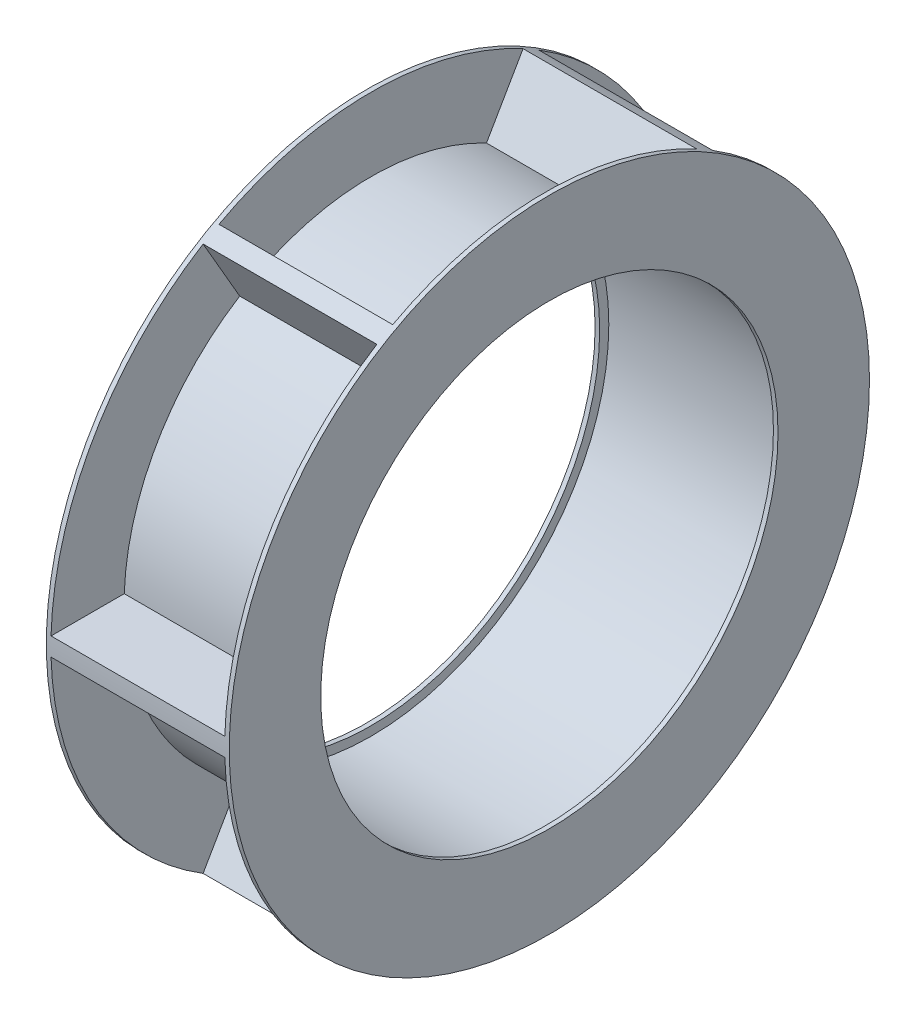
SolidWorks part; units mm, degrees
material "1060 Alloy"
ref_plane "Front Plane" through (0, 0, 0) normal (1, 0, 0) x (0, 1, 0)
ref_plane "Top Plane" through (0, 0, 0) normal (0, 0, 1) x (0, 1, 0)
ref_plane "Right Plane" through (0, 0, 0) normal (0, 1, 0) x (-1, 0, 0)
sketch "Sketch8" plane through (0, 0, 0) normal (1, 0, 0) x (0, 1, 0)
  circle A0 centre (0, 0) radius 125
  circle A1 centre (0, 0) radius 175
  dimension "D1" = 250
  dimension "D2" = 50
extrude "Boss-Extrude7" add sketch "Sketch8" along normal mid plane 100
sketch "Sketch9" plane through (0, 0, 0) normal (1, 0, 0) x (0, 1, 0)
  circle A0 centre (0, 0) radius 125 construction
  circle A1 centre (0, 0) radius 125
  circle A2 centre (0, 0) radius 130
  dimension "D1" = 5
extrude "Cut-Extrude2" cut sketch "Sketch9" against normal mid plane 95
sketch "Sketch10" plane through (50, 0, 0) normal (1, 0, 0) x (0, 1, 0)
  line L0 (0, -1000) -> (0, 49000) construction
  line L1 (149.0544, 91.8301) -> (110, 69.282)
  line L2 (-5, 175) -> (5, 175)
  line L3 (-5, 175) -> (-5, 129.9038)
  line L4 (-5, 129.9038) -> (5, 129.9038)
  line L5 (5, 175) -> (5, 129.9038)
  line L6 (149.0544, 91.8301) -> (154.0544, 83.1699)
  line L7 (154.0544, 83.1699) -> (115, 60.6218)
  line L8 (110, 69.282) -> (115, 60.6218)
  line L9 (154.0544, -83.1699) -> (115, -60.6218)
  line L10 (154.0544, -83.1699) -> (149.0544, -91.8301)
  line L11 (149.0544, -91.8301) -> (110, -69.282)
  line L12 (115, -60.6218) -> (110, -69.282)
  line L13 (5, -175) -> (5, -129.9038)
  line L14 (5, -175) -> (-5, -175)
  line L15 (-5, -175) -> (-5, -129.9038)
  line L16 (5, -129.9038) -> (-5, -129.9038)
  line L17 (-149.0544, -91.8301) -> (-110, -69.282)
  line L18 (-149.0544, -91.8301) -> (-154.0544, -83.1699)
  line L19 (-154.0544, -83.1699) -> (-115, -60.6218)
  line L20 (-110, -69.282) -> (-115, -60.6218)
  line L21 (-154.0544, 83.1699) -> (-115, 60.6218)
  line L22 (-154.0544, 83.1699) -> (-149.0544, 91.8301)
  line L23 (-149.0544, 91.8301) -> (-110, 69.282)
  line L24 (-115, 60.6218) -> (-110, 69.282)
  circle A0 centre (0, 0) radius 175 construction
  circle A1 centre (0, 0) radius 175
  circle A3 centre (0, 0) radius 130 construction
  circle A4 centre (0, 0) radius 135
  point P12 (0, 0)
  point P13 (0, 0)
  point P35 (0, 0)
  circle M12 centre (0, 0) radius 175
  dimension "D4" = 260
  dimension "D5" = 260
  dimension "D1" = 10
  dimension "D2" = 6
  dimension "D3" = 5
extrude "Cut-Extrude3" cut sketch "Sketch10" against normal through all both and the other way through all contours A3 L1 L5 M12 | A3 L9 L7 M12 | A3 L13 L11 M12 | A3 L17 L15 M12 | A3 L21 L19 M12 | A3 L3 L23 M12 region at (50, 74.8569, 129.656) region at (50, 149.7138, 0) region at (50, -74.8569, 129.656) region at (50, 74.8569, -129.656) region at (50, -149.7138, 0) region at (50, -74.8569, -129.656)
sketch "Sketch11" plane through (50, 0, 0) normal (1, 0, 0) x (0, 1, 0)
  circle A0 centre (0, 0) radius 125 construction
  circle A1 centre (0, 0) radius 125
  circle A2 centre (0, 0) radius 175
  dimension "D1" = 250
extrude "Boss-Extrude8" add sketch "Sketch11" against normal blind 2.5
mirror "Mirror3" about plane through (0, 0, 0) normal (1, 0, 0) of "Boss-Extrude8"
sketch "Sketch2" plane through (0, 0, 0) normal (1, 0, 0) x (0, 1, 0)
  line L0 (0, -1000) -> (0, 125) construction
  line L8 (-7.5, 23.8485) -> (-7.5, 125)
  line L9 (-7.5, 125) -> (7.5, 125)
  line L10 (7.5, 23.8485) -> (7.5, 125)
  line L11 (20.3636, 14.5025) -> (116.5644, 45.76)
  line L13 (24.9989, 0.2367) -> (121.1997, 31.4942)
  line L14 (116.5644, 45.76) -> (121.1997, 31.4942)
  line L15 (20.0854, -14.8854) -> (79.5408, -96.7187)
  line L17 (7.9502, -23.7022) -> (67.4055, -105.5355)
  line L18 (79.5408, -96.7187) -> (67.4055, -105.5355)
  line L19 (-7.9502, -23.7022) -> (-67.4055, -105.5355)
  line L21 (-20.0854, -14.8854) -> (-79.5408, -96.7187)
  line L22 (-67.4055, -105.5355) -> (-79.5408, -96.7187)
  line L23 (-24.9989, 0.2367) -> (-121.1997, 31.4942)
  line L25 (-20.3636, 14.5025) -> (-116.5644, 45.76)
  line L26 (-121.1997, 31.4942) -> (-116.5644, 45.76)
  line L31 (-962.4087, -312.7056) -> (118.8821, 38.6271) construction
  circle A0 centre (0, 0) radius 10
  circle A7 centre (0, 0) radius 25
  point P17 (0, 125)
  point P40 (0, 0)
  dimension "D1" = 20
  dimension "D2" = 50
  dimension "D3" = 125
  dimension "D4" = 15
  dimension "D6" = 125
  dimension "D5" = 5
extrude "Boss-Extrude1" [suppressed] add sketch "Sketch2" along normal mid plane 100
sketch "Sketch4" [suppressed] plane through (50, 0, 0) normal (1, 0, 0) x (0, 1, 0)
  line L0 (0, -1000) -> (0, 49000) construction
  line L1 (-1000, 0) -> (49000, 0) construction
  line L3 (-7.5, 125) -> (7.5, 125) construction
  circle A4 centre (0, 0) radius 125
  circle A5 centre (0, 0) radius 165
  dimension "D1" = 330
extrude "Boss-Extrude3" [suppressed] add sketch "Sketch4" against normal up to surface (100 mm away)
sketch "Sketch5" [suppressed] plane through (50, 0, 0) normal (1, 0, 0) x (0, 1, 0)
  line L0 (0, -1000) -> (0, 49000) construction
  line L34 (114.8915, 118.427) -> (90.1257, 93.6613)
  line L35 (-2.5, 165) -> (2.5, 165)
  line L36 (-2.5, 165) -> (-2.5, 129.976)
  line L37 (-2.5, 129.976) -> (2.5, 129.976)
  line L38 (2.5, 165) -> (2.5, 129.976)
  line L39 (114.8915, 118.427) -> (118.427, 114.8915)
  line L40 (118.427, 114.8915) -> (93.6613, 90.1257)
  line L41 (90.1257, 93.6613) -> (93.6613, 90.1257)
  line L42 (164.9677, 2.4866) -> (129.9436, 2.4866)
  line L43 (164.9677, 2.4866) -> (164.9677, -2.5134)
  line L44 (164.9677, -2.5134) -> (129.9436, -2.5134)
  line L45 (129.9436, 2.4866) -> (129.9436, -2.5134)
  line L46 (118.3947, -114.9049) -> (93.6289, -90.1391)
  line L47 (118.3947, -114.9049) -> (114.8591, -118.4404)
  line L48 (114.8591, -118.4404) -> (90.0934, -93.6746)
  line L49 (93.6289, -90.1391) -> (90.0934, -93.6746)
  line L50 (2.4543, -164.9811) -> (2.4543, -129.957)
  line L51 (2.4543, -164.9811) -> (-2.5457, -164.9811)
  line L52 (-2.5457, -164.9811) -> (-2.5457, -129.957)
  line L53 (2.4543, -129.957) -> (-2.5457, -129.957)
  line L54 (-114.9372, -118.4081) -> (-90.1714, -93.6423)
  line L55 (-114.9372, -118.4081) -> (-118.4727, -114.8725)
  line L56 (-118.4727, -114.8725) -> (-93.707, -90.1068)
  line L57 (-90.1714, -93.6423) -> (-93.707, -90.1068)
  line L58 (-165.0134, -2.4677) -> (-129.9894, -2.4677)
  line L59 (-165.0134, -2.4677) -> (-165.0134, 2.5323)
  line L60 (-165.0134, 2.5323) -> (-129.9894, 2.5323)
  line L61 (-129.9894, -2.4677) -> (-129.9894, 2.5323)
  line L62 (-118.4404, 114.9238) -> (-93.6746, 90.1581)
  line L63 (-118.4404, 114.9238) -> (-114.9049, 118.4593)
  line L64 (-114.9049, 118.4593) -> (-90.1391, 93.6936)
  line L65 (-93.6746, 90.1581) -> (-90.1391, 93.6936)
  circle A1 centre (0, 0) radius 130
  arc A3 (116.3503, 45.6905) -> (7.5, 124.7748) centre (0, 0) ccw construction
  circle A4 centre (0, 0) radius 165 construction
  circle A5 centre (0, 0) radius 165
  point P44 (-0.0229, 0.0095)
  dimension "D1" = 5
  dimension "D2" = 5
  dimension "D3" = 8
extrude "Cut-Extrude1" [suppressed] cut sketch "Sketch5" against normal blind 120
sketch "Sketch7" [suppressed] plane through (50, 0, 0) normal (1, 0, 0) x (0, 1, 0)
  circle A3 centre (0, 0) radius 130
  arc A4 (129.9762, 2.4866) -> (93.6746, 90.1391) centre (0, 0) ccw construction
  circle A5 centre (0, 0) radius 165
extrude "Boss-Extrude6" [suppressed] add sketch "Sketch7" against normal blind 4
mirror "Mirror2" [suppressed] about plane through (0, 0, 0) normal (1, 0, 0)
sketch "Sketch6" [suppressed] plane through (60, 0, 0) normal (1, 0, 0) x (0, 1, 0)
  line L0 (-14.4338, 25) -> (-28.8675, 0) construction
  line L1 (-28.8675, 0) -> (-14.4338, -25) construction
  line L2 (-14.4338, -25) -> (14.4338, -25) construction
  line L3 (14.4338, -25) -> (28.8675, 0) construction
  line L4 (28.8675, 0) -> (14.4338, 25) construction
  line L5 (14.4338, 25) -> (-14.4338, 25) construction
  line L6 (-14.4338, 25) -> (-28.8675, 0)
  line L7 (-28.8675, 0) -> (-14.4338, -25)
  line L8 (-14.4338, -25) -> (14.4338, -25)
  line L9 (14.4338, -25) -> (28.8675, 0)
  line L10 (28.8675, 0) -> (14.4338, 25)
  line L11 (14.4338, 25) -> (-14.4338, 25)
  circle A0 centre (0, 0) radius 150
extrude "Boss-Extrude4" [suppressed] add sketch "Sketch6" along normal blind 4
mirror "Mirror1" [suppressed] about plane through (0, 0, 0) normal (1, 0, 0)
